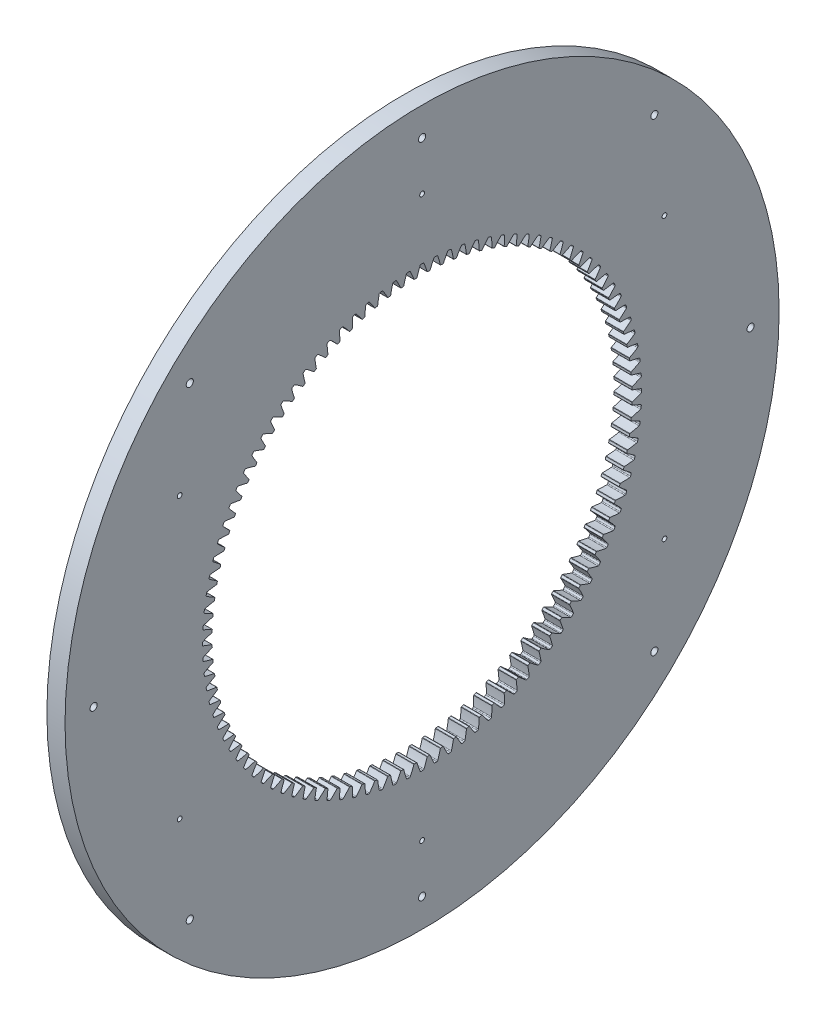
SolidWorks part; units mm, degrees
material "6061 Alloy"
ref_plane "Plane1" through (0, 0, 0) normal (0, 0, 1) x (1, 0, 0)
ref_plane "Plane2" through (0, 0, 0) normal (0, 1, 0) x (1, 0, 0)
ref_plane "Plane3" through (0, 0, 0) normal (1, 0, 0) x (0, 0, -1)
sketch "HoldingSke" plane through (0, 0, 0) normal (0, 1, 0) x (1, 0, 0)
  line L0 (0, 0) -> (-0.0579, -0.3283)
  line L1 (-15, 0) -> (100, 0) construction
  line L2 (0, 0) -> (-2.1039, 2.3779)
  line L3 (0, 0) -> (-11.863, 4.5341)
  line L4 (0, 0) -> (-1.4996, 8.5048)
  line L5 (0, 0) -> (-23.7986, -8.8762)
  line L6 (0, 0) -> (-10.5278, -7.1032)
  line L7 (-2.1039, 2.3779) -> (3.3635, 27.1825)
  line L8 (-76.2, 5.3779) -> (-54.61, 5.3779)
  line L9 (-71.009, 38.7566) -> (-53.1078, 45.2721)
  line L10 (-76.2, 71.12) -> (104.1128, 71.12)
  line L11 (0, 0) -> (-12.7, 0)
  line L12 (-76.2, 101.6) -> (-76.093, 101.6)
  line L13 (24.9733, 27.94) -> (52.9518, 28.4284)
  line L14 (24.9733, 27.94) -> (24.9743, 27.94)
  line L15 (24.9733, 27.94) -> (100.4006, 29.5858)
  circle A0 centre (0, 0) radius 250
  circle A1 centre (0, 0) radius 12.7
  circle A2 centre (0, 0) radius 12.7
  dimension "Num_teeth" = 100
  dimension "Pitch_radius" = 180.3128
  dimension "Width" = 12.7
  dimension "Thickness" = 12.7
  dimension "Diameter" = 500
sketch "BasProSke" plane through (0, 0, 0) normal (0, 1, 0) x (1, 0, 0)
  line L0 (-10, 0) -> (60, 0) construction
  line L1 (0, 147) -> (0, 250)
  line L2 (0, 147) -> (12.7, 147)
  line L3 (12.7, 147) -> (12.7, 250)
  line L4 (12.7, 250) -> (0, 250)
  dimension "Thickness" = 12.7
  dimension "Diameter" = 500
revolve "Base-Revolve" add sketch "BasProSke" angle 360 about L0
sketch "TooCutSke" plane through (0, 0, 0) normal (1, 0, 0) x (0, 0, -1)
  line L3 (2.6236, 149.9771) -> (2.6236, 53.6633) construction
  line L4 (0, 0) -> (0, 59.563) construction
  line L5 (0, 0) -> (-2.1462, 68.2938) construction
  line L6 (-68.0184, 124.7836) -> (33.8394, 127.9846) construction
  circle A0 centre (0, 0) radius 150 construction
  circle A1 centre (0, 0) radius 153.751 construction
  circle A2 centre (0, 0) radius 126.8585 construction
  circle A3 centre (0, 0) radius 146.9746 construction
  arc A4 (3.6374, 146.9296) -> (1.1636, 153.7466) centre (-68.0184, 124.7836) ccw
  arc A5 (3.6374, 146.9296) -> (-3.6374, 146.9296) centre (0, 0) ccw
  arc A6 (1.1636, 153.7466) -> (-1.1636, 153.7466) centre (0, 0) ccw
  arc A7 (-1.1636, 153.7466) -> (-3.6374, 146.9296) centre (68.0184, 124.7836) ccw
extrude "ToothCut" cut sketch "TooCutSke" along normal through all
fillet "Breaks" radius 0.3 2 edges at (6.35, 146.9552, 3.6295) (6.35, 146.9552, -3.6295)
fillet "RootFillets" radius 0.751 2 edges at (6.35, 153.7466, 1.1636) (6.35, 153.7466, -1.1636)
pattern_circular "TeethCuts" count 100 every 3.6 about axis through (-10, 0, 0) along (1, 0, 0) of "RootFillets", "Breaks", "ToothCut"
sketch "Sketch2" plane through (12.7, 0, 0) normal (1, 0, 0) x (0, 0, -1)
  circle A0 centre (0, 0) radius 230
  circle A1 centre (0, 0) radius 196
  circle A2 centre (0, 196) radius 2
  circle A3 centre (0, 230) radius 3
  circle A4 centre (169.741, 98) radius 2
  circle A5 centre (169.741, -98) radius 2
  circle A6 centre (0, -196) radius 2
  circle A7 centre (-169.741, -98) radius 2
  circle A8 centre (-169.741, 98) radius 2
  circle A9 centre (162.6346, 162.6346) radius 3
  circle A10 centre (230, 0) radius 3
  circle A11 centre (162.6346, -162.6346) radius 3
  circle A12 centre (0, -230) radius 3
  circle A13 centre (-162.6346, -162.6346) radius 3
  circle A14 centre (-230, 0) radius 3
  circle A15 centre (-162.6346, 162.6346) radius 3
  point P9 (-166.6418, 198.7335)
  point P10 (0, 0)
  point P21 (0, 0)
  point P35 (0, 0)
  dimension "D1" = 460
  dimension "D2" = 392
  dimension "D3" = 4
  dimension "D4" = 6
  dimension "D5" = 6
  dimension "D6" = 8
hole_wizard "Tap Drill for M6x1.0 Tap1" positions "3DSketch1" profile "Sketch3" hole size "M6x1.0" standard "ANSI Metric" end condition through all
sketch3d "3DSketch1"
  point P0 (12.7, 230, 0)
  point P6 (12.7, 162.6346, 162.6346)
  point P9 (12.7, 162.6346, -162.6346)
  point P11 (12.7, 0, 230)
  point P13 (12.7, 0, -230)
  point P15 (12.7, -162.6346, 162.6346)
  point P17 (12.7, -230, 0)
  point P19 (12.7, -162.6346, -162.6346)
  point P22 (12.7, 162.6346, 162.6346)
  point P24 (12.7, 0, 230)
  point P26 (12.7, 162.6346, -162.6346)
  point P28 (12.7, 0, -230)
  point P30 (12.7, -162.6346, -162.6346)
  point P32 (12.7, -230, 0)
  point P34 (12.7, -162.6346, 162.6346)
sketch "Sketch3" plane through (12.7, 230, 0) normal (0, 1, 0) x (0, 0, -1)
  line L0 (0, 0) -> (0, 12.7)
  line L1 (0, 12.7) -> (2.5, 12.7)
  line L2 (2.5, 12.7) -> (2.5, 0)
  line L5 (2.5, 0) -> (0, 0)
  line L11 (0, -6.35) -> (0, 107.95) construction
  dimension "Thru Hole Dia." = 5
  dimension "Thru Hole Depth" = 12.7
hole_wizard "Tap Drill for M4x0.7 Tap1" positions "3DSketch2" profile "Sketch4" hole size "M4x0.7" standard "ANSI Metric" end condition through all
sketch3d "3DSketch2"
  point P0 (12.7, 196, 0)
  point P5 (12.7, 98, 169.741)
  point P7 (12.7, -98, 169.741)
  point P9 (12.7, -196, 0)
  point P11 (12.7, -98, -169.741)
  point P13 (12.7, 98, -169.741)
  point P16 (12.7, 98, 169.741)
  point P18 (12.7, -98, 169.741)
  point P20 (12.7, -196, 0)
  point P22 (12.7, -98, -169.741)
  point P24 (12.7, 98, -169.741)
sketch "Sketch4" plane through (12.7, 196, 0) normal (0, 1, 0) x (0, 0, -1)
  line L0 (0, 0) -> (0, 12.7)
  line L1 (0, 12.7) -> (1.65, 12.7)
  line L2 (1.65, 12.7) -> (1.65, 0)
  line L5 (1.65, 0) -> (0, 0)
  line L11 (0, -6.35) -> (0, 107.95) construction
  dimension "Thru Hole Dia." = 3.3
  dimension "Thru Hole Depth" = 12.7
equation "\"Pitch@HoldingSke\" = 1 / \"Module@HoldingSke\" "
equation "\"Overcut_dia@TooCutSke\" = (\"Num_teeth@HoldingSke\" - 2 * \"Addendum_fac@HoldingSke\") / \"Pitch@HoldingSke\" - 0.002 * 25.4"
equation "\"Pitch_dia@TooCutSke\" = \"Num_teeth@HoldingSke\" / \"Pitch@HoldingSke\""
equation "\"Base_dia@TooCutSke\" = \"Num_teeth@HoldingSke\" / \"Pitch@HoldingSke\" * cos((\"Ap@HoldingSke\"  * 3.14159265 / 180)) * 0.90"
equation "\"Root_dia@TooCutSke\" = \"Num_teeth@HoldingSke\"  / \"Pitch@HoldingSke\" + 2 *  \"Dedendum_fac@HoldingSke\"/ \"Pitch@HoldingSke\" + \"Dedendum_add@HoldingSke\" * 2"
equation "\"Half_ang@TooCutSke\" = 180 / \"Num_teeth@HoldingSke\""
equation "\"Half_CT@TooCutSke\" = \"Num_teeth@HoldingSke\" / \"Pitch@HoldingSke\" * sin((3.14159265 / 2 / \"Num_teeth@HoldingSke\")) / 2 + 10 * \"Backlash@HoldingSke\" / 4"
equation "\"Flank_rad@TooCutSke\" = \"Num_teeth@HoldingSke\" / \"Pitch@HoldingSke\" / 4"
equation "\"Radius@RootFillets\"= \"Clearance_fac@HoldingSke\" / \"Pitch@HoldingSke\" + \"Dedendum_add@HoldingSke\""
equation "\"Break_rad@Breaks\" = 0.02 / \"Pitch@HoldingSke\" * 5"
equation "\"Num_teeth@TeethCuts\" = int( \"Show_teeth@HoldingSke\" ) + 1"
equation "\"Num_teeth@TeethCuts\" = ((sgn( \"Num_teeth@TeethCuts\" - \"Num_teeth@HoldingSke\" )-1)*( \"Num_teeth@TeethCuts\" - \"Num_teeth@HoldingSke\" ))/-2+ \"Num_teeth@HoldingSke\""
equation "\"Num_teeth@TeethCuts\" = ((sgn( \"Num_teeth@TeethCuts\" - 2.0)+1)*( \"Num_teeth@TeethCuts\" - 2.0))/2 +2.0"
equation "\"Angle@TeethCuts\" = 360.0 / \"Num_teeth@HoldingSke\""
equation "\"Diameter@BasProSke\" = \"Num_teeth@HoldingSke\"  / \"Pitch@HoldingSke\" + 2 *  \"Dedendum_fac@HoldingSke\"/ \"Pitch@HoldingSke\" + \"Dedendum_add@HoldingSke\" * 2 + 0.002 * 25.4"
equation "\"Diameter@BasProSke\" = ((sgn( \"Diameter@BasProSke\"  - \"Diameter@HoldingSke\" )+1)*( \"Diameter@BasProSke\"  - \"Diameter@HoldingSke\" ))/2 + \"Diameter@HoldingSke\""
equation "\"Inside_diameter@BasProSke\" =  (\"Num_teeth@HoldingSke\" - 2 * \"Addendum_fac@HoldingSke\") / \"Pitch@HoldingSke\" "
equation "\"Thickness@BasProSke\"  = \"Width@HoldingSke\""
